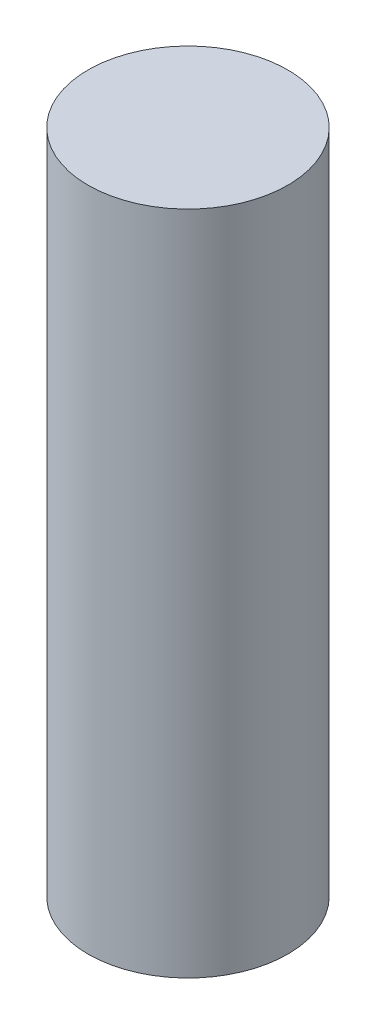
SolidWorks part; units mm, degrees
material "Сталь 3 ГОСТ 535-88"
ref_plane "Спереди" through (0, 0, 0) normal (0, 0, 1) x (1, 0, 0)
ref_plane "Сверху" through (0, 0, 0) normal (0, 1, 0) x (1, 0, 0)
ref_plane "Справа" through (0, 0, 0) normal (1, 0, 0) x (0, 0, -1)
sketch "Эскиз1" plane through (0, 0, 0) normal (0, 1, 0) x (1, 0, 0)
  circle A0 centre (0, 0) radius 3
  dimension "D1" = 6
extrude "Бобышка-Вытянуть1" add sketch "Эскиз1" along normal blind 10 and the other way blind 10
sketch "Эскиз2" plane through (0, 0, 0) normal (1, 0, 0) x (0, 0, -1)
  line L0 (0, -19.6379) -> (0, 19.6379) construction
  point P3 (0, 0)
